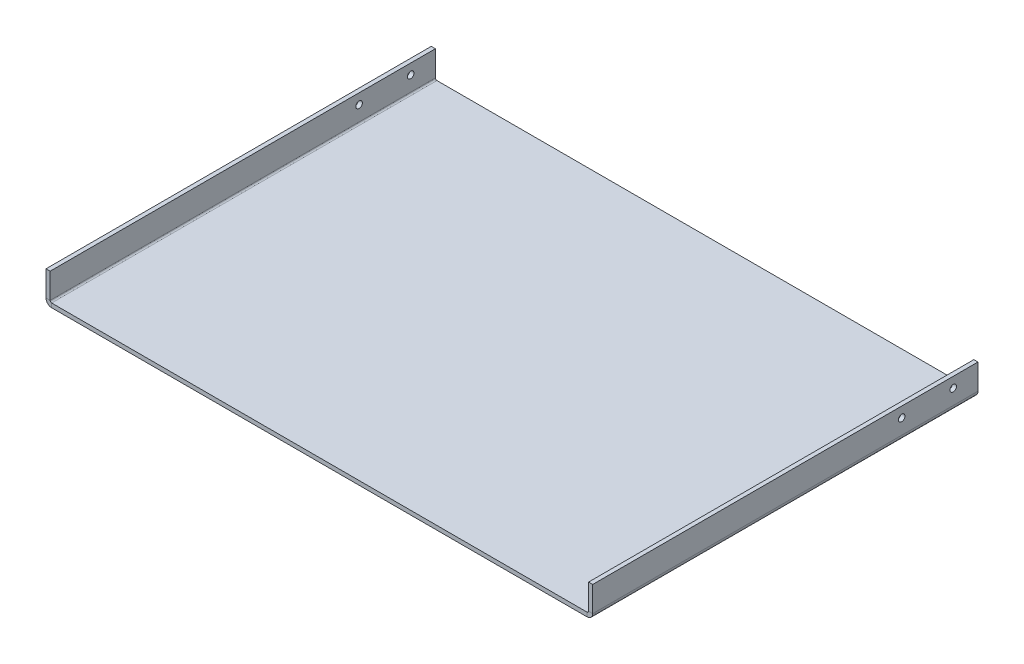
SolidWorks part; units mm, degrees
note: The reader was unsure of these and kept them because the rebuilt part matched: flange length of "Ребро-кромка1".
ref_plane "Спереди" through (0, 0, 0) normal (0, 0, 1) x (1, 0, 0)
ref_plane "Сверху" through (0, 0, 0) normal (0, 1, 0) x (1, 0, 0)
ref_plane "Справа" through (0, 0, 0) normal (1, 0, 0) x (0, 0, -1)
sketch "Эскиз1" plane through (0, 0, 0) normal (0, 1, 0) x (1, 0, 0)
  line L1 (-223.496, 31.5017) -> (41.504, 31.5017)
  line L2 (-223.496, 31.5017) -> (-223.496, -155.2483)
  line L3 (-223.496, -155.2483) -> (41.504, -155.2483)
  line L4 (41.504, 31.5017) -> (41.504, -155.2483)
  dimension "D1" = 265
  dimension "D2" = 186.75
base flange "Базовая кромка1" sketch "Эскиз1" thickness 2 reverse thickness direction no parameters "D1"=0.7366
edge flange "Ребро-кромка1" sketch "Эскиз10" flange profiles "Эскиз10", "Эскиз11" flange angle 90 flange length 15 flange position material inside bend radius 0.7366 thickness 2 relief rectangular parameters "D6"=10, "D8"=1
sketch "Эскиз10" plane through (-223.496, 0, 0) normal (-1, 0, 0) x (0, 0, 1)
  line L2 (-31.5017, 0) -> (-31.5017, 13)
  line L3 (-31.5017, 13) -> (155.2483, 13)
  line L4 (155.2483, 13) -> (155.2483, 0)
  line L5 (-31.5017, 0) -> (155.2483, 0) construction
  line L6 (-31.5017, 0) -> (155.2483, 0)
sketch "Эскиз11" plane through (41.504, 0, 0) normal (1, 0, 0) x (0, 0, -1)
  line L0 (-155.2483, 0) -> (31.5017, 0) construction
  line L1 (-155.2483, 0) -> (31.5017, 0)
  line L2 (-155.2483, 0) -> (-155.2483, 13)
  line L3 (-155.2483, 13) -> (31.5017, 13)
  line L4 (31.5017, 13) -> (31.5017, 0)
bend "EdgeBend1" bend radius 0.7366 bend angle 90 parameters "D5"=1
bend "EdgeBend2" bend radius 0.7366 bend angle 90 parameters "D5"=2
sketch "Эскиз12" plane through (-223.496, 0, 0) normal (-1, 0, 0) x (0, 0, 1)
  line L0 (-31.5017, 13) -> (-31.5017, 0.7366) construction
  line L1 (155.2483, 13) -> (-31.5017, 13) construction
  line L3 (-19.5017, 8) -> (6.2065, 8) construction
  circle A0 centre (-19.5017, 8) radius 1.6
  circle A1 centre (5.4983, 8) radius 1.6
  dimension "D1" = 3.2
  dimension "D2" = 12
  dimension "D3" = 5
  dimension "D4" = 3.2
  dimension "D5" = 25
extrude "Вырез-Вытянуть1" cut sketch "Эскиз12" against normal blind 281 normal cut yes
sketch "Сгиб-Линии1" plane through (0, 0, 0) normal (0, 1, 0) x (1, 0, 0)
sketch "Граничная рамка1" plane through (0, 0, 0) normal (0, 1, 0) x (1, 0, 0)
sheet metal parameters "Листовой металл3" thickness 2 parameters "D1"=0.7366
flat pattern "Развертка3" [suppressed]
sketch "Сгиб-Линии2" plane through (0, 0, 0) normal (0, 1, 0) x (1, 0, 0)
sketch "Граничная рамка2" [suppressed] plane through (0, 0, 0) normal (0, 1, 0) x (1, 0, 0)
sheet metal parameters "Листовой металл4" thickness 2 parameters "D1"=0.7366
flat pattern "Развертка3" [suppressed]
sketch "Сгиб-Линии2" plane through (0, 0, 0) normal (0, 1, 0) x (1, 0, 0)
sketch "Граничная рамка2" [suppressed] plane through (0, 0, 0) normal (0, 1, 0) x (1, 0, 0)
bend of the flat pattern "Плоское состояние-<EdgeBend1>1"
bend of the flat pattern "Плоское состояние-<EdgeBend2>1"
sheet metal parameters "Листовой металл5" thickness 2 parameters "D1"=0.7366
flat pattern "Развертка3" [suppressed]
sketch "Сгиб-Линии2" plane through (0, 0, 0) normal (0, 1, 0) x (1, 0, 0)
sketch "Граничная рамка2" [suppressed] plane through (0, 0, 0) normal (0, 1, 0) x (1, 0, 0)
bend of the flat pattern "Плоское состояние-<EdgeBend1>1"
bend of the flat pattern "Плоское состояние-<EdgeBend2>1"
